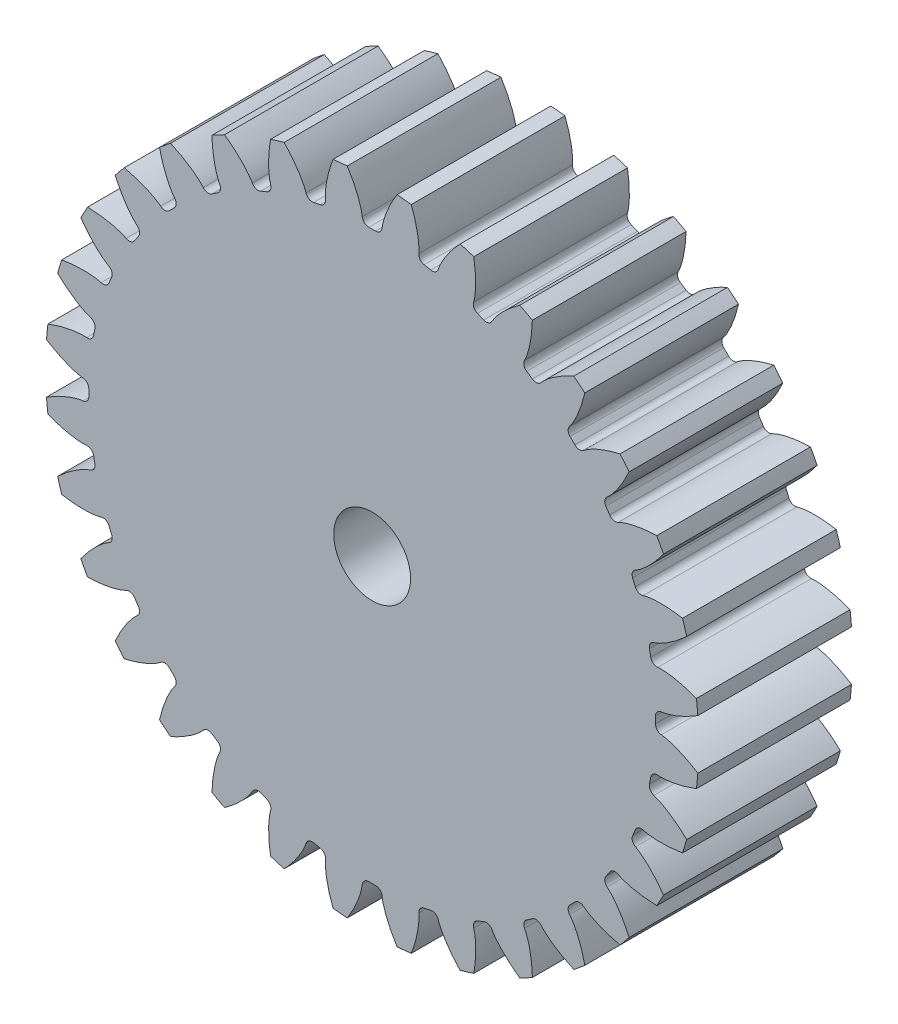
SolidWorks part; units mm, degrees
ref_plane "Front Plane" through (0, 0, 0) normal (0, 0, 1) x (1, 0, 0)
ref_plane "Top Plane" through (0, 0, 0) normal (0, 1, 0) x (1, 0, 0)
ref_plane "Right Plane" through (0, 0, 0) normal (1, 0, 0) x (0, 0, -1)
sketch "Sketch1" plane through (0, 0, 0) normal (0, 0, 1) x (1, 0, 0)
  line L0 (0, 0) -> (0, 25.4) construction
  line L1 (-8.1634, 28.3712) -> (8.1634, 22.4288) construction
  circle A0 centre (0, 0) radius 23.4156 construction
  circle A1 centre (0, 0) radius 26.9875 construction
  circle A2 centre (0, 0) radius 25.4 construction
  circle A3 centre (0, 0) radius 23.8682 construction
  circle A4 centre (0, 0) radius 3.175 construction
  circle A5 centre (0, 0) radius 6.35 construction
  point P8 (203.2, 0)
  point P13 (406.4, 0)
  dimension "OD | Outside Diameter" = 53.975
  dimension "Root Diameter" = 46.8312
  dimension "Gear Pitch Diameter" = 50.8
  dimension "Base Diameter" = 47.7364
  dimension "For Shaft Diameter" = 6.35
  dimension "Hub Diameter" = 12.7
  dimension "Pressure Angle" = 20
  dimension "Number of Teeth" = 812.8
  dimension "Gear Pitch | Diametral Pitch" = 406.4
sketch "Sketch2" plane through (0, 0, 0) normal (1, 0, 0) x (0, 0, -1)
  line L0 (-6.35, 0) -> (6.35, 0) construction
  line L1 (-6.35, 26.9875) -> (6.35, 26.9875) construction
  point P2 (0, 26.9875)
  point P4 (-5.715, 0)
  point P6 (-5.715, 26.9875)
  dimension "Overall Width" = 12.7
  dimension "Face Width" = 12.065
sketch "Sketch3" plane through (0, 0, 0) normal (0, 0, 1) x (1, 0, 0)
  circle A0 centre (0, 0) radius 26.9875
  circle A1 centre (0, 0) radius 26.9875 construction
extrude "Boss-Extrude1" add sketch "Sketch3" against normal up to vertex (6.35 mm away) and the other way up to vertex (6.35 mm away) up to point (0, 0, -6.35) other way up to point (0, 0, 6.35)
sketch "Sketch5" plane through (0, 0, 0) normal (1, 0, 0) x (0, 0, -1)
  line L11 (6.35, 3.175) -> (-6.35, 3.175)
  line L12 (6.35, 3.175) -> (6.35, 0)
  line L13 (6.35, 0) -> (-6.35, 0)
  line L14 (-6.35, 3.175) -> (-6.35, 0)
  point P5 (0, 3.175)
revolve "Cut-Revolve1" cut sketch "Sketch5" angle 360 about L0
sketch "Sketch4" plane through (0, 0, 0) normal (0, 0, 1) x (1, 0, 0)
  line L0 (0, 0) -> (23.4019, 0.8003) construction
  line L2 (0, 0) -> (23.4019, -0.8003) construction
  line L4 (23.4019, 0.8003) -> (23.8542, 0.8157)
  line L5 (23.8542, -0.8157) -> (23.4019, -0.8003)
  arc A0 (23.4019, 0.8003) -> (23.4019, -0.8003) centre (0, 0) cw
  arc A3 (26.9089, 2.0577) -> (26.9089, -2.0577) centre (0, 0) cw
  circle A4 centre (0, 0) radius 26.9875 construction
  spline S0 degree 4 poles (23.8542, 0.8157) (23.8592, 0.816) (23.8729, 0.8167) (23.8989, 0.8189) (23.9413, 0.8234) (23.9952, 0.8305) (24.0647, 0.8414) (24.1465, 0.8562) (24.2362, 0.8746) (24.3337, 0.897) (24.4306, 0.9214) (24.5272, 0.9477) (24.6232, 0.9756) (24.7393, 1.0114) (24.8782, 1.0572) (25.04, 1.1149) (25.2228, 1.1851) (25.4085, 1.2619) (25.5905, 1.3418) (25.7737, 1.4274) (25.9504, 1.5136) (26.1331, 1.6083) (26.3013, 1.6982) (26.4888, 1.8044) (26.6399, 1.8918) (26.838, 2.0129) (26.9547, 2.0862) (27.0909, 2.1739) (27.1512, 2.214) (27.1883, 2.2386) knots 0 0 0 0 0 0.005377 0.015084 0.028532 0.04661 0.064855 0.092111 0.119476 0.146842 0.174209 0.201575 0.228941 0.256307 0.307035 0.361767 0.4165 0.471232 0.525964 0.580697 0.635429 0.690161 0.744894 0.799626 0.854358 0.909091 0.954545 1 1 1 1 1 construction
  spline S1 degree 4 poles (23.8542, 0.8157) (23.8592, 0.816) (23.8729, 0.8167) (23.8989, 0.8189) (23.9413, 0.8234) (23.9952, 0.8305) (24.0647, 0.8414) (24.1465, 0.8562) (24.2362, 0.8746) (24.3337, 0.897) (24.4306, 0.9214) (24.5272, 0.9477) (24.6232, 0.9756) (24.7393, 1.0114) (24.8782, 1.0572) (25.04, 1.1149) (25.2228, 1.1851) (25.4085, 1.2619) (25.5905, 1.3418) (25.7737, 1.4274) (25.9504, 1.5136) (26.1331, 1.6083) (26.3013, 1.6982) (26.4888, 1.8044) (26.6399, 1.8918) (26.7951, 1.9866) (26.8705, 2.0335) (26.9089, 2.0577) knots 0 0 0 0 0 0.005377 0.015084 0.028532 0.04661 0.064855 0.092111 0.119476 0.146842 0.174209 0.201575 0.228941 0.256307 0.307035 0.361767 0.4165 0.471232 0.525964 0.580697 0.635429 0.690161 0.744894 0.799626 0.854358 0.909091 0.909091 0.909091 0.909091 0.909091
  spline S2 degree 4 poles (23.8542, -0.8157) (23.8592, -0.816) (23.8729, -0.8167) (23.8989, -0.8189) (23.9413, -0.8234) (23.9952, -0.8305) (24.0647, -0.8414) (24.1465, -0.8562) (24.2362, -0.8746) (24.3337, -0.897) (24.4306, -0.9214) (24.5272, -0.9477) (24.6232, -0.9756) (24.7393, -1.0114) (24.8782, -1.0572) (25.04, -1.1149) (25.2228, -1.1851) (25.4085, -1.2619) (25.5905, -1.3418) (25.7737, -1.4274) (25.9504, -1.5136) (26.1331, -1.6083) (26.3013, -1.6982) (26.4888, -1.8044) (26.6399, -1.8918) (26.838, -2.0129) (26.9547, -2.0862) (27.0909, -2.1739) (27.1512, -2.214) (27.1883, -2.2386) knots 0 0 0 0 0 0.005377 0.015084 0.028532 0.04661 0.064855 0.092111 0.119476 0.146842 0.174209 0.201575 0.228941 0.256307 0.307035 0.361767 0.4165 0.471232 0.525964 0.580697 0.635429 0.690161 0.744894 0.799626 0.854358 0.909091 0.954545 1 1 1 1 1 construction
  spline S3 degree 4 poles (23.8542, -0.8157) (23.8592, -0.816) (23.8729, -0.8167) (23.8989, -0.8189) (23.9413, -0.8234) (23.9952, -0.8305) (24.0647, -0.8414) (24.1465, -0.8562) (24.2362, -0.8746) (24.3337, -0.897) (24.4306, -0.9214) (24.5272, -0.9477) (24.6232, -0.9756) (24.7393, -1.0114) (24.8782, -1.0572) (25.04, -1.1149) (25.2228, -1.1851) (25.4085, -1.2619) (25.5905, -1.3418) (25.7737, -1.4274) (25.9504, -1.5136) (26.1331, -1.6083) (26.3013, -1.6982) (26.4888, -1.8044) (26.6399, -1.8918) (26.7951, -1.9866) (26.8705, -2.0335) (26.9089, -2.0577) knots 0 0 0 0 0 0.005377 0.015084 0.028532 0.04661 0.064855 0.092111 0.119476 0.146842 0.174209 0.201575 0.228941 0.256307 0.307035 0.361767 0.4165 0.471232 0.525964 0.580697 0.635429 0.690161 0.744894 0.799626 0.854358 0.909091 0.909091 0.909091 0.909091 0.909091
  dimension "D1" = 46.8312
extrude "Cut-Extrude1" cut sketch "Sketch4" against normal through all both and the other way through all
fillet "Fillet1" radius 0.5326 2 edges at (23.4019, -0.8003, 0) (23.4019, 0.8003, 0)
pattern_circular "CirPattern1" count 32 over 360 about axis through (0, 0, 6.35) along (0, 0, -1) of "Cut-Extrude1", "Fillet1"
equation "\"Root Diameter@Sketch1\"=\"Root Diameter\""
equation "\"OD | Outside Diameter@Sketch1\"=\"Outside Diameter\""
equation "\"D1@CirPattern1\"=\"Number of Teeth\""
equation "\"Diametral Pitch\"= 16"
equation "\"Number of Teeth\"= 32"
equation "\"Pressure Angle\"=20"
equation "\"Pitch Diameter\"= \"Number of Teeth\" / \"Diametral Pitch\""
equation "\"Base Diameter\"= \"Pitch Diameter\" * cos ( \"Pressure Angle\" )"
equation "\"Outside Diameter\"= ( \"Number of Teeth\" + 2 ) / \"Diametral Pitch\""
equation "\"Dedendum\"= 1.25 / \"Diametral Pitch\""
equation "\"Root Diameter\"= \"Pitch Diameter\" - ( 2 * \"Dedendum\" )"
equation "\"Pitch Angle\"= 360deg / \"Number of Teeth\""
equation "\"Alpha\"= sqr ( \"Pitch Diameter\" ^ 2 - \"Base Diameter\" ^ 2 ) / \"Base Diameter\" * 180 / PI - \"Pressure Angle\""
equation "\"Beta\"= ( \"Pitch Angle\" / 4 - \"Alpha\" )"
equation "\"Phi\"= sqr ( ( \"Outside Diameter\" / 2 ) ^ 2 - ( \"Base Diameter\" / 2 ) ^ 2 ) / ( \"Base Diameter\" / 2 )"
equation "\"Addendum\"= 1 / \"Diametral Pitch\""
equation "\"WorkingDepth\"= 2 / \"Diametral Pitch\""
equation "\"WholeDepth\"= 2.25 / \"Diametral Pitch\""
equation "\"Clearance\"= 0.25 / \"Diametral Pitch\""
equation "\"ToothThickness\"= ( pi * 2 ) / \"Diametral Pitch\""
equation "\"CircularPitch\"= pi / \"Diametral Pitch\""
equation "\"Number of Teeth@Sketch1\"=\"Number of Teeth\""
equation "\"Gear Pitch | Diametral Pitch@Sketch1\"=\"Diametral Pitch\""
equation "\"Pressure Angle@Sketch1\"=\"Pressure Angle\""
equation "\"Gear Pitch Diameter@Sketch1\"=\"Pitch Diameter\""
equation "\"Base Diameter@Sketch1\"=\"Base Diameter\""
equation "\"Fillet\"= \"Clearance\" * cos ( \"Pressure Angle\" ) * tan ( ( 90 + \"Pressure Angle\" ) / 2 )"
equation "\"D1@Fillet1\"=\"Fillet\""
equation "\"D1@Sketch4\"=if( \"Base Diameter\">\"Root Diameter\",\"Root Diameter\",\"Base Diameter\"-.00001)"
equation "\"D1@Fillet2\"=\"Fillet\""
